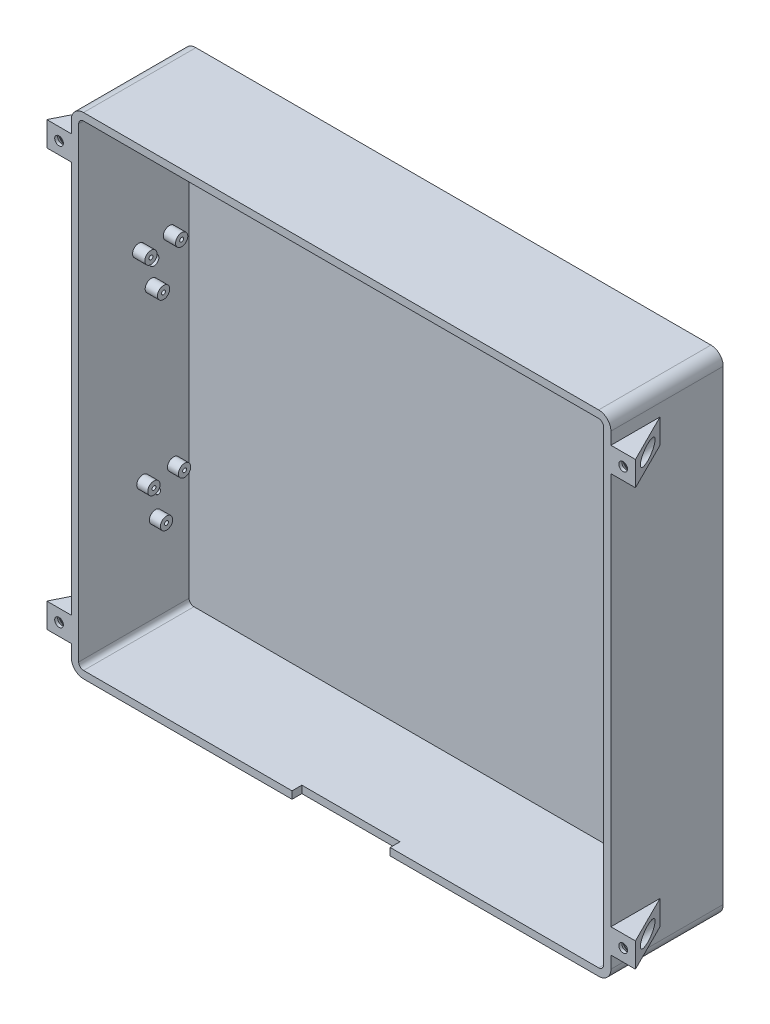
SolidWorks part; units mm, degrees
ref_plane "Front Plane" through (0, 0, 0) normal (0, 0, 1) x (1, 0, 0)
ref_plane "Top Plane" through (0, 0, 0) normal (0, 1, 0) x (1, 0, 0)
ref_plane "Right Plane" through (0, 0, 0) normal (1, 0, 0) x (0, 0, -1)
sketch "Sketch2" plane through (0, 0, 0) normal (0, 0, 1) x (1, 0, 0)
  line L5 (139.7, 127) -> (-139.7, 127)
  line L6 (139.7, 127) -> (139.7, -127)
  line L7 (139.7, -127) -> (-139.7, -127)
  line L8 (-139.7, 127) -> (-139.7, -127)
  line L9 (139.7, 127) -> (-139.7, -127) construction
  line L10 (139.7, -127) -> (-139.7, 127) construction
  point P0 (0, 0)
  dimension "D1" = 254
  dimension "D2" = 279.4
extrude "Boss-Extrude1" add sketch "Sketch2" along normal blind 1
fillet "Fillet2" radius 6.35 4 edges at (139.7, -127, 0.5) (-139.7, -127, 0.5) (-139.7, 127, 0.5) (139.7, 127, 0.5)
sketch "Sketch5" plane through (0, 0, 1) normal (0, 0, 1) x (1, 0, 0)
  line L0 (-133.35, -123.19) -> (133.35, -123.19)
  line L1 (135.89, -120.65) -> (135.89, 120.65)
  line L2 (133.35, 123.19) -> (-133.35, 123.19)
  line L3 (-135.89, 120.65) -> (-135.89, -120.65)
  line L4 (-133.35, -127) -> (133.35, -127)
  line L5 (139.7, -120.65) -> (139.7, 120.65)
  line L6 (133.35, 127) -> (-133.35, 127)
  line L7 (-139.7, 120.65) -> (-139.7, -120.65)
  line L8 (-133.35, -127) -> (133.35, -127)
  line L9 (139.7, -120.65) -> (139.7, 120.65)
  line L10 (133.35, 127) -> (-133.35, 127)
  line L11 (-139.7, 120.65) -> (-139.7, -120.65)
  arc A0 (133.35, -123.19) -> (135.89, -120.65) centre (133.35, -120.65) ccw
  arc A1 (135.89, 120.65) -> (133.35, 123.19) centre (133.35, 120.65) ccw
  arc A2 (-133.35, 123.19) -> (-135.89, 120.65) centre (-133.35, 120.65) ccw
  arc A3 (-135.89, -120.65) -> (-133.35, -123.19) centre (-133.35, -120.65) ccw
  arc A4 (133.35, -127) -> (139.7, -120.65) centre (133.35, -120.65) ccw
  arc A5 (139.7, 120.65) -> (133.35, 127) centre (133.35, 120.65) ccw
  arc A6 (-133.35, 127) -> (-139.7, 120.65) centre (-133.35, 120.65) ccw
  arc A7 (-139.7, -120.65) -> (-133.35, -127) centre (-133.35, -120.65) ccw
  arc A8 (133.35, -127) -> (139.7, -120.65) centre (133.35, -120.65) ccw
  arc A9 (139.7, 120.65) -> (133.35, 127) centre (133.35, 120.65) ccw
  arc A10 (-133.35, 127) -> (-139.7, 120.65) centre (-133.35, 120.65) ccw
  arc A11 (-139.7, -120.65) -> (-133.35, -127) centre (-133.35, -120.65) ccw
  dimension "D1" = 0
  dimension "D2" = 3.81
extrude "Boss-Extrude3" add sketch "Sketch5" along normal blind 57.15
sketch "Sketch7" plane through (0, -123.19, 0) normal (0, 1, 0) x (1, 0, 0)
  line L0 (-133.35, -58.15) -> (133.35, -58.15) construction
  line L1 (25.4, -58.15) -> (-25.4, -58.15)
  line L2 (25.4, -58.15) -> (25.4, -53.07)
  line L3 (25.4, -53.07) -> (-25.4, -53.07)
  line L4 (-25.4, -58.15) -> (-25.4, -53.07)
  point P6 (0, -58.15)
  dimension "D1" = 5.08
  dimension "D2" = 50.8
extrude "Cut-Extrude1" cut sketch "Sketch7" against normal blind 57.15
ref_plane "Plane1" through (0, 101.6, 0) normal (0, 1, 0) x (1, 0, 0)
sketch "Sketch8" plane through (0, 101.6, 0) normal (0, 1, 0) x (1, 0, 0)
  line L0 (-139.7, 0) -> (-152.4, 0)
  line L1 (-152.4, 0) -> (-139.7, -25.4)
  line L2 (-139.7, -58.15) -> (-139.7, 0) construction
  line L3 (-139.7, -25.4) -> (-139.7, 0)
  line L4 (139.7, 0) -> (139.7, -25.4) construction
  line L5 (139.7, 0) -> (139.7, -58.15) construction
  line L6 (139.7, -25.4) -> (152.4, 0) construction
  line L7 (152.4, 0) -> (139.7, 0) construction
  dimension "D1" = 12.7
  dimension "D2" = 25.4
extrude "Boss-Extrude4" add sketch "Sketch8" along normal blind 12.7
ref_plane "Plane2" through (0, 0, 3.81) normal (0, 0, -1) x (-1, 0, 0)
sketch "Sketch9" plane through (0, 0, 3.81) normal (0, 0, -1) x (-1, 0, 0)
  line L0 (152.4, 114.3) -> (152.4, 101.6) construction
  line L1 (152.4, 114.3) -> (152.4, 101.6)
  line L2 (152.4, 107.95) -> (146.05, 107.95)
  circle A0 centre (146.05, 107.95) radius 3.81
  dimension "D1" = 7.62
  dimension "D2" = 6.35
extrude "Cut-Extrude2" cut sketch "Sketch9" against normal blind 35.306 contours A0
hole_wizard "CSK for #8 Flat Head Machine Screw1" positions "Sketch12" profile "Sketch13" countersink size "#8" standard "ANSI Inch" end condition through all
sketch "Sketch12" plane through (0, 0, 3.81) normal (0, 0, 1) x (1, 0, 0)
  point P0 (-146.05, 107.95)
sketch "Sketch13" plane through (-146.05, 107.95, 3.81) normal (1, 0, 0) x (0, -1, 0)
  line L0 (0, 0) -> (0, 3.81)
  line L1 (0, 3.81) -> (2.2479, 3.81)
  line L2 (2.2479, 3.81) -> (2.2479, 2.2645)
  line L3 (2.2479, 2.2645) -> (4.2164, 0)
  line L5 (4.2164, 0) -> (0, 0)
  line L6 (-2.2479, 2.2645) -> (-4.2164, 0) construction
  line L11 (0, -6.35) -> (0, 107.95) construction
  dimension "Thru Hole Dia." = 4.4958
  dimension "Thru Hole Depth" = 3.81
  dimension "Near C'Sink Dia." = 8.4328
  dimension "Near C'Sink Angle" = 82
sketch "Sketch14" plane through (0, 0, 3.81) normal (0, 0, -1) x (-1, 0, 0)
  line L1 (159.8523, 111.76) -> (146.05, 111.76)
  line L2 (159.8523, 111.76) -> (159.8523, 104.14)
  line L3 (159.8523, 104.14) -> (146.05, 104.14)
  line L4 (146.05, 111.76) -> (146.05, 104.14)
  circle A0 centre (146.05, 107.95) radius 2.2479 construction
  circle A1 centre (146.05, 107.95) radius 2.2479 construction
  circle A2 centre (146.05, 107.95) radius 3.81 construction
ref_plane "Plane3" through (0, 0, 0) normal (0, 1, 0) x (1, 0, 0)
mirror "Mirror2" about plane through (0, 0, 0) normal (0, 1, 0) of "Cut-Extrude2", "CSK for #8 Flat Head Machine Screw1", "Boss-Extrude4"
ref_plane "Plane4" through (0, 0, 0) normal (-1, 0, 0) x (0, 0, 1)
mirror "Mirror3" about plane through (0, 0, 0) normal (-1, 0, 0) of "Mirror2", "CSK for #8 Flat Head Machine Screw1", "Cut-Extrude2", "Boss-Extrude4"
ref_plane "Plane5" through (0, 0, 29.075) normal (0, 0, -1) x (-1, 0, 0)
mirror "Mirror4" about plane through (0, 0, 29.075) normal (0, 0, -1) of "Mirror3", "Mirror2", "CSK for #8 Flat Head Machine Screw1", "Cut-Extrude2", "Boss-Extrude4"
sketch "Sketch15" plane through (0, 0, 0) normal (0, 0, -1) x (-1, 0, 0)
  line L1 (-152.4, 114.3) -> (-139.7, 114.3)
  line L2 (-152.4, 114.3) -> (-152.4, -114.3)
  line L3 (-152.4, -114.3) -> (-139.7, -114.3)
  line L4 (-139.7, 114.3) -> (-139.7, -114.3)
  line L5 (152.4, -114.3) -> (139.7, -114.3)
  line L6 (152.4, -114.3) -> (152.4, 114.3)
  line L7 (152.4, 114.3) -> (139.7, 114.3)
  line L8 (139.7, -114.3) -> (139.7, 114.3)
extrude "Cut-Extrude4" cut sketch "Sketch15" against normal blind 30.226
sketch "Sketch17" [suppressed] plane through (0, 127, 0) normal (0, 1, 0) x (1, 0, 0)
  line L4 (98.4433, -33.0881) -> (98.4433, -48.0233)
  line L5 (98.4433, -48.0233) -> (119.2713, -48.0233)
  line L6 (119.2713, -48.0233) -> (119.2713, -33.0881)
  line L7 (119.2713, -33.0881) -> (98.4433, -33.0881)
  line L8 (98.4433, -33.0881) -> (98.4433, -48.0233)
  line L9 (98.4433, -48.0233) -> (119.2713, -48.0233)
  line L10 (119.2713, -48.0233) -> (119.2713, -33.0881)
  line L11 (119.2713, -33.0881) -> (98.4433, -33.0881)
  circle A0 centre (120.6088, -28.8966) radius 1.632 construction
  circle A1 centre (37.8048, -28.8966) radius 1.632 construction
  circle A2 centre (-3.292, -15.605) radius 6.9215 construction
  circle A3 centre (120.6088, -28.8966) radius 1.632
  circle A4 centre (37.8048, -28.8966) radius 1.632
  circle A5 centre (-3.292, -15.605) radius 6.9215
  dimension "D1" = 0
sketch "Sketch18" [suppressed] plane through (0, 123.19, 0) normal (0, -1, 0) x (1, 0, 0)
  line L0 (133.35, 1) -> (-133.35, 1) construction
  line L1 (47.3298, 1) -> (28.2798, 1)
  line L2 (111.0838, 1) -> (111.0838, 28.8966)
  line L3 (130.1338, 28.8966) -> (130.1338, 1)
  line L4 (130.1338, 1) -> (111.0838, 1)
  line L5 (28.2798, 1) -> (28.2798, 28.8966)
  line L6 (47.3298, 28.8966) -> (47.3298, 1)
  line L7 (47.3298, 1) -> (28.2798, 1)
  line L8 (130.1338, 1) -> (111.0838, 1)
  arc A2 (111.0838, 28.8966) -> (130.1338, 28.8966) centre (120.6088, 28.8966) cw
  arc A3 (28.2798, 28.8966) -> (47.3298, 28.8966) centre (37.8048, 28.8966) cw
  line M2 (-133.35, 1) -> (133.35, 1)
  dimension "D1" = 9.525
extrude "Boss-Extrude5" [suppressed] add sketch "Sketch18" along normal blind 12.7 contours A2 L2 L3 M2 | A3 L5 L6 M2
sketch "Sketch19" [suppressed] plane through (0, 127, 0) normal (0, 1, 0) x (1, 0, 0)
  circle A0 centre (120.6088, -28.8966) radius 1.27
  circle A1 centre (37.8048, -28.8966) radius 1.27
  dimension "D1" = 2.54
extrude "Cut-Extrude5" [suppressed] cut sketch "Sketch19" against normal up to next
sketch "Sketch24" plane through (-139.7, 0, 0) normal (-1, 0, 0) x (0, 0, 1)
  circle A2 centre (19.1168, 39.9413) radius 2.5019
  circle A3 centre (19.1168, 39.9413) radius 2.5019
  dimension "D1" = 0.762
extrude "Cut-Extrude8" cut sketch "Sketch24" against normal up to next
sketch "Sketch27" plane through (-135.89, 0, 0) normal (1, 0, 0) x (0, 0, -1)
  circle A0 centre (-20.5316, 29.4101) radius 0.9652 construction
  circle A1 centre (-11.1679, 48.3902) radius 1.035 construction
  circle A2 centre (-27.0658, 48.3902) radius 1.0351 construction
  circle A6 centre (-20.5316, 29.4101) radius 0.9652 construction
  circle A7 centre (-11.1679, 48.3902) radius 1.035 construction
  circle A8 centre (-27.0658, 48.3902) radius 1.0351 construction
  circle A15 centre (-27.0658, 48.3902) radius 3.175
  circle A16 centre (-11.1679, 48.3902) radius 3.175
  circle A17 centre (-20.5316, 29.4101) radius 3.175
  dimension "D1" = 6.35
ref_plane "Plane6" through (-130.175, -61.8785, 19.956) normal (0, 1, 0) x (1, 0, 0)
sketch "Sketch30" plane through (-139.7, 0, 0) normal (-1, 0, 0) x (0, 0, 1)
  circle A0 centre (16.956, -64.8785) radius 1.7399 construction
  circle A1 centre (16.956, -64.8785) radius 1.7399 construction
  circle A2 centre (16.956, -64.8785) radius 1.27
  dimension "D1" = 2.54
extrude "Cut-Extrude10" cut sketch "Sketch30" against normal up to next
extrude "Boss-Extrude6" add sketch "Sketch27" along normal up to surface (6.35 mm away)
sketch "Sketch28" plane through (-135.89, 0, 0) normal (1, 0, 0) x (0, 0, -1)
  circle A0 centre (-9.007, -56.4296) radius 1.035 construction
  circle A1 centre (-24.9049, -56.4296) radius 1.0351 construction
  circle A2 centre (-18.3708, -75.4097) radius 0.9652 construction
  circle A3 centre (-9.007, -56.4296) radius 1.035 construction
  circle A4 centre (-24.9049, -56.4296) radius 1.0351 construction
  circle A5 centre (-18.3708, -75.4097) radius 0.9652 construction
  circle A6 centre (-18.3708, -75.4097) radius 3.175
  circle A7 centre (-24.9049, -56.4296) radius 3.175
  circle A8 centre (-9.007, -56.4296) radius 3.175
  dimension "D1" = 6.35
extrude "Boss-Extrude7" add sketch "Sketch28" along normal up to surface (5.715 mm away)
sketch "Sketch33" plane through (-129.54, 0, 0) normal (1, 0, 0) x (0, 0, -1)
  point P0 (-27.0658, 48.3902)
  point P1 (-11.1679, 48.3902)
  point P3 (-20.5316, 29.4101)
hole_wizard "#3 (0.213) Diameter Hole1" positions "Sketch34" profile "Sketch36" hole size "#3" standard "ANSI Inch"
sketch "Sketch34" plane through (-129.54, 0, 0) normal (1, 0, 0) x (0, 0, -1)
  point P0 (-27.0658, 48.3902)
  point P4 (-11.1679, 48.3902)
  point P7 (-20.5316, 29.4101)
sketch "Sketch36" plane through (-129.54, 48.3902, 27.0658) normal (0, 1, 0) x (0, 0, -1)
  line L0 (0, 0) -> (0, 6.9605)
  line L1 (0, 6.9605) -> (1.016, 6.35)
  line L2 (1.016, 6.35) -> (1.016, 0)
  line L5 (1.016, 0) -> (0, 0)
  line L10 (0, 6.9605) -> (-1.016, 6.35) construction
  line L11 (0, -6.35) -> (0, 107.95) construction
  dimension "Hole Dia." = 2.032
  dimension "Hole Depth" = 6.35
  dimension "Drill Angle" = 118
hole_wizard "#3 (0.213) Diameter Hole2" positions "Sketch37" profile "Sketch38" hole size "#3" standard "ANSI Inch"
sketch "Sketch37" plane through (-130.175, 0, 0) normal (1, 0, 0) x (0, 0, -1)
  point P0 (-24.9049, -56.4296)
  point P3 (-9.007, -56.4296)
  point P6 (-18.3708, -75.4097)
sketch "Sketch38" plane through (-130.175, -56.4296, 24.9049) normal (0, 1, 0) x (0, 0, -1)
  line L0 (0, 0) -> (0, 6.9605)
  line L1 (0, 6.9605) -> (1.016, 6.35)
  line L2 (1.016, 6.35) -> (1.016, 0)
  line L5 (1.016, 0) -> (0, 0)
  line L10 (0, 6.9605) -> (-1.016, 6.35) construction
  line L11 (0, -6.35) -> (0, 107.95) construction
  dimension "Hole Dia." = 2.032
  dimension "Hole Depth" = 6.35
  dimension "Drill Angle" = 118
